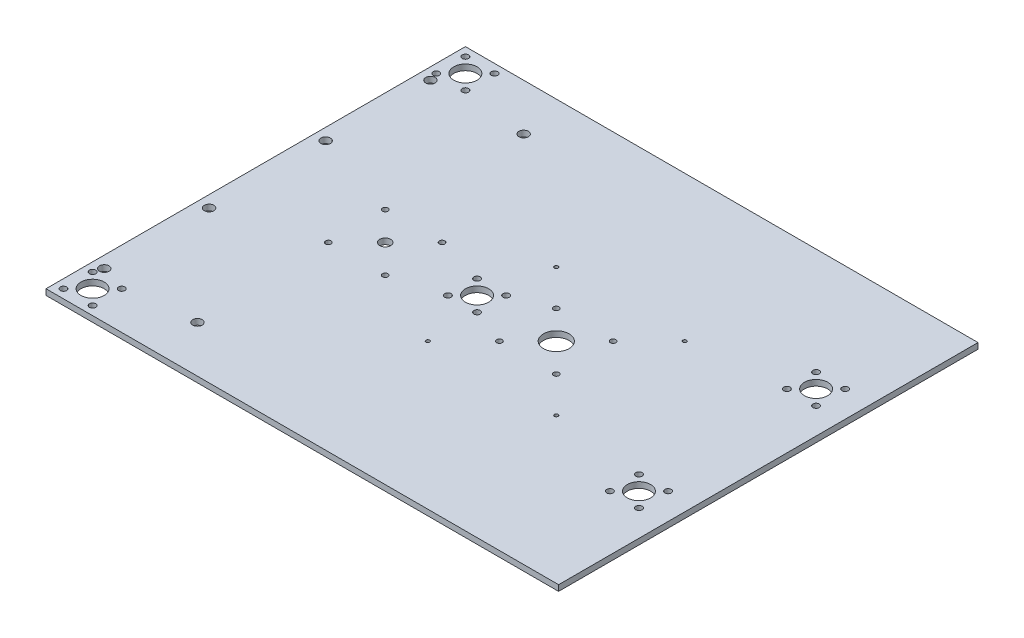
SolidWorks part; units mm, degrees
ref_plane "Front Plane" through (0, 0, 0) normal (0, 0, 1) x (1, 0, 0)
ref_plane "Top Plane" through (0, 0, 0) normal (0, 1, 0) x (1, 0, 0)
ref_plane "Right Plane" through (0, 0, 0) normal (1, 0, 0) x (0, 0, -1)
sketch "Sketch1" plane through (0, 0, 0) normal (0, 1, 0) x (1, 0, 0)
  line L1 (-139.7, -114.3) -> (139.7, -114.3)
  line L2 (-139.7, -114.3) -> (-139.7, 114.3)
  line L3 (-139.7, 114.3) -> (139.7, 114.3)
  line L4 (139.7, -114.3) -> (139.7, 114.3)
  line L5 (-139.7, -114.3) -> (139.7, 114.3) construction
  line L6 (-139.7, 114.3) -> (139.7, -114.3) construction
  point P0 (0, 0)
  dimension "D1" = 228.6
  dimension "D2" = 279.4
extrude "Boss-Extrude1" add sketch "Sketch1" along normal blind 3.175
sketch "Sketch2" plane through (0, 0, 0) normal (0, 1, 0) x (1, 0, 0)
  line L0 (-193.2668, 0) -> (192.9727, 0) construction
sketch "Sketch3" plane through (0, 3.175, 0) normal (0, 1, 0) x (1, 0, 0)
  circle A1 centre (-133.35, -31.75) radius 2.6
  circle A2 centre (-133.35, -31.75) radius 2.6
  circle A3 centre (-82.55, -88.9) radius 2.6
  circle A4 centre (-82.55, -88.9) radius 2.6
  circle A5 centre (-133.35, -88.9) radius 2.6
  circle A6 centre (-133.35, -88.9) radius 2.6
  dimension "D1" = 0
  dimension "D2" = 0
  dimension "D3" = 0
sketch "Sketch5" plane through (0, 3.175, 0) normal (0, 1, 0) x (1, 0, 0)
  circle A0 centre (-53.612, 15.5) radius 1.5 construction
  circle A1 centre (-53.612, -15.5) radius 1.5 construction
  circle A2 centre (-84.612, 15.5) radius 1.5 construction
  circle A3 centre (-84.612, -15.5) radius 1.5 construction
  circle A4 centre (-69.112, 0) radius 2.5 construction
  circle A5 centre (-53.612, 15.5) radius 1.5
  circle A6 centre (-53.612, -15.5) radius 1.5
  circle A7 centre (-84.612, 15.5) radius 1.5
  circle A8 centre (-84.612, -15.5) radius 1.5
  circle A9 centre (-69.112, 0) radius 2.5 construction
  circle A10 centre (-69.112, 0) radius 3
  dimension "D1" = 6
sketch "Sketch7" plane through (0, 3.175, 0) normal (0, 1, 0) x (1, 0, 0)
  circle A0 centre (59.1318, -35.0018) radius 1 construction
  circle A1 centre (-10.8718, -35.0018) radius 1 construction
  circle A2 centre (59.1318, -35.0018) radius 1
  circle A3 centre (-10.8718, -35.0018) radius 1
  circle A4 centre (-10.8718, 35.0018) radius 1 construction
  circle A5 centre (59.1318, 35.0018) radius 1 construction
  circle A6 centre (-10.8718, 35.0018) radius 1
  circle A7 centre (59.1318, 35.0018) radius 1
extrude "Cut-Extrude1" cut sketch "Sketch3" against normal through all
mirror "Mirror1" about plane through (0, 0, 0) normal (0, 0, 1) of "Cut-Extrude1"
extrude "Cut-Extrude2" cut sketch "Sketch5" against normal through all
extrude "Cut-Extrude3" cut sketch "Sketch7" against normal through all
sketch "Sketch9" plane through (0, 3.175, 0) normal (0, 1, 0) x (1, 0, 0)
  circle A0 centre (-119.0625, -109.5375) radius 1.727 construction
  circle A1 centre (-119.0625, -93.6625) radius 1.727 construction
  circle A2 centre (-134.9375, -93.6625) radius 1.727 construction
  circle A3 centre (-134.9375, -109.5375) radius 1.727 construction
  circle A4 centre (-127, -101.6) radius 6.35 construction
  circle A5 centre (-119.0625, -109.5375) radius 1.727
  circle A6 centre (-119.0625, -93.6625) radius 1.727
  circle A7 centre (-134.9375, -93.6625) radius 1.727
  circle A8 centre (-134.9375, -109.5375) radius 1.727
  circle A9 centre (-127, -101.6) radius 6.35
  circle A10 centre (125.4125, -56.1975) radius 1.727 construction
  circle A11 centre (125.4125, -40.3225) radius 1.727 construction
  circle A12 centre (117.475, -48.26) radius 6.35 construction
  circle A13 centre (109.5375, -40.3225) radius 1.727 construction
  circle A14 centre (109.5375, -56.1975) radius 1.727 construction
  circle A15 centre (125.4125, -56.1975) radius 1.727
  circle A16 centre (125.4125, -40.3225) radius 1.727
  circle A17 centre (117.475, -48.26) radius 6.35
  circle A18 centre (109.5375, -40.3225) radius 1.727
  circle A19 centre (109.5375, -56.1975) radius 1.727
  circle A20 centre (-11.1125, 7.9375) radius 1.727 construction
  circle A21 centre (-11.1125, -7.9375) radius 1.727 construction
  circle A22 centre (-19.05, 0) radius 6.35 construction
  circle A23 centre (-26.9875, -7.9375) radius 1.727 construction
  circle A24 centre (-26.9875, 7.9375) radius 1.727 construction
  circle A25 centre (-11.1125, 7.9375) radius 1.727
  circle A26 centre (-11.1125, -7.9375) radius 1.727
  circle A27 centre (-19.05, 0) radius 6.35
  circle A28 centre (-26.9875, -7.9375) radius 1.727
  circle A29 centre (-26.9875, 7.9375) radius 1.727
  circle A30 centre (109.5375, 56.1975) radius 1.727 construction
  circle A31 centre (109.5375, 40.3225) radius 1.727 construction
  circle A32 centre (125.4125, 56.1975) radius 1.727 construction
  circle A33 centre (117.475, 48.26) radius 6.35 construction
  circle A34 centre (125.4125, 40.3225) radius 1.727 construction
  circle A35 centre (109.5375, 56.1975) radius 1.727
  circle A36 centre (109.5375, 40.3225) radius 1.727
  circle A37 centre (125.4125, 56.1975) radius 1.727
  circle A38 centre (117.475, 48.26) radius 6.35
  circle A39 centre (125.4125, 40.3225) radius 1.727
  circle A40 centre (-119.0625, 93.6625) radius 1.727 construction
  circle A41 centre (-119.0625, 109.5375) radius 1.727 construction
  circle A42 centre (-134.9375, 109.5375) radius 1.727 construction
  circle A43 centre (-134.9375, 93.6625) radius 1.727 construction
  circle A44 centre (-119.0625, 93.6625) radius 1.727
  circle A45 centre (-119.0625, 109.5375) radius 1.727
  circle A46 centre (-134.9375, 109.5375) radius 1.727
  circle A47 centre (-134.9375, 93.6625) radius 1.727
  circle A48 centre (-127, 101.6) radius 6.35 construction
  circle A49 centre (-127, 101.6) radius 6.35
extrude "Cut-Extrude5" cut sketch "Sketch9" against normal through all both and the other way through all
sketch "Sketch11" plane through (0, 3.175, 0) normal (0, 1, 0) x (1, 0, 0)
  circle A0 centre (39.63, 15.5) radius 1.5 construction
  circle A1 centre (39.63, -15.5) radius 1.5 construction
  circle A2 centre (8.63, -15.5) radius 1.5 construction
  circle A3 centre (8.63, 15.5) radius 1.5 construction
  circle A4 centre (24.13, 0) radius 5.25 construction
  circle A5 centre (39.63, 15.5) radius 1.5
  circle A6 centre (39.63, -15.5) radius 1.5
  circle A7 centre (8.63, -15.5) radius 1.5
  circle A8 centre (8.63, 15.5) radius 1.5
  circle A9 centre (24.13, 0) radius 5.25 construction
  circle A10 centre (24.13, 0) radius 6.985
  dimension "D1" = 13.97
extrude "Cut-Extrude6" cut sketch "Sketch11" against normal through all both and the other way through all
equation "\"tightTol\"= 0.005in"
equation "\"normTol\"= 0.01in"
equation "\"looseTol\"= 0.02in"
equation "\"D1@Sketch5\"=6mm"
